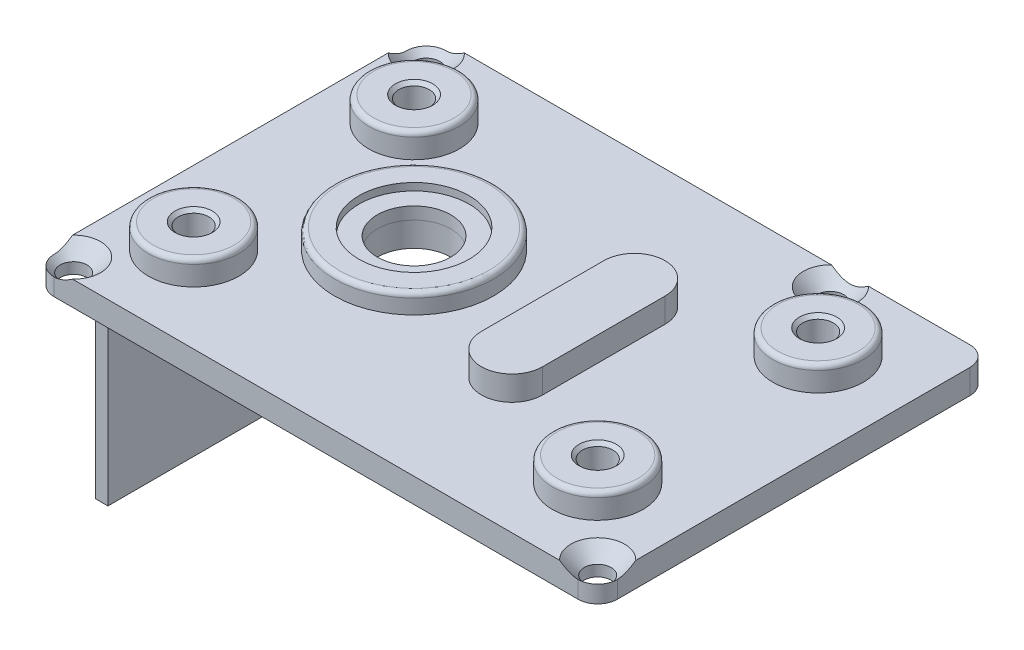
SolidWorks part; units mm, degrees
material "201.0-T7 Insulated Mold Casting (SS)"
ref_plane "Front Plane" through (0, 0, 0) normal (0, 0, 1) x (1, 0, 0)
ref_plane "Top Plane" through (0, 0, 0) normal (0, 1, 0) x (1, 0, 0)
ref_plane "Right Plane" through (0, 0, 0) normal (1, 0, 0) x (0, 0, -1)
sketch "Sketch2" plane through (0, 0, 0) normal (0, 1, 0) x (1, 0, 0)
  line L0 (0, 0) -> (-15, 0) construction
  line L1 (-15, 16) -> (31, 16)
  line L2 (-15, 16) -> (-15, -16)
  line L3 (-15, -16) -> (31, -16)
  line L4 (31, 16) -> (31, -16)
  dimension "D1" = 32
  dimension "D2" = 46
  dimension "D3" = 15
extrude "Boss-Extrude2" add sketch "Sketch2" along normal blind 2
sketch "Sketch6" plane through (0, 2, 0) normal (0, 1, 0) x (1, 0, 0)
  circle A0 centre (0, 0) radius 3
  dimension "D1" = 6
extrude "Cut-Extrude1" cut sketch "Sketch6" against normal through all
sketch "Sketch7" plane through (0, 2, 0) normal (0, 1, 0) x (1, 0, 0)
  circle A0 centre (0, 0) radius 4.5
  circle A1 centre (0, 0) radius 3
  circle A2 centre (0, 0) radius 3 construction
  dimension "D1" = 9
extrude "Boss-Extrude4" add sketch "Sketch7" along normal blind 1 separate body
sketch "Sketch8" plane through (0, 2, 0) normal (0, 1, 0) x (1, 0, 0)
  circle A0 centre (0, 0) radius 4.5
  circle A1 centre (0, 0) radius 4.5 construction
  circle A2 centre (0, 0) radius 6.5
  dimension "D1" = 13
extrude "Boss-Extrude5" add sketch "Sketch8" along normal blind 1.6 separate body
sketch "Sketch3" plane through (0, 2, 0) normal (0, 1, 0) x (1, 0, 0)
  line L0 (-15, 0) -> (31, 0) construction
  line L1 (-15, 16) -> (-15, -16) construction
  line L2 (31, -16) -> (31, 16) construction
  line L3 (8, -16) -> (8, 16) construction
  line L4 (-15, -16) -> (31, -16) construction
  line L5 (31, 16) -> (-15, 16) construction
  circle A0 centre (-9, 9) radius 3.7
  circle A2 centre (0, 0) radius 3 construction
  dimension "D1" = 7.4
  dimension "D2" = 6
  dimension "D4" = 9
  dimension "D3" = 7
  dimension "D5" = 9
extrude "Boss-Extrude3" add sketch "Sketch3" along normal blind 2
fillet "Fillet3" radius 0.4 1 edges at (0, 3.6, 6.5)
ref_plane "MP HORZ HOLES" through (8, 0, 0) normal (-1, 0, 0) x (0, 0, 1)
hole_wizard "M3x0.5 Tapped Hole1" positions "Sketch5" profile "Sketch4" tap size "M3x0.5" standard "ANSI Metric" end condition through all
sketch "Sketch5" plane through (0, 4, 0) normal (0, 1, 0) x (1, 0, 0)
  point P0 (-9, 9)
sketch "Sketch4" plane through (-9, 4, -9) normal (1, 0, 0) x (0, 0, 1)
  line L0 (0, 0) -> (0, 4)
  line L1 (0, 4) -> (1.25, 4)
  line L2 (1.25, 4) -> (1.25, 0.275)
  line L3 (1.25, 0.275) -> (1.525, 0)
  line L5 (1.525, 0) -> (0, 0)
  line L6 (-1.25, 0.275) -> (-1.525, 0) construction
  line L11 (0, -6.35) -> (0, 107.95) construction
  dimension "Thread Major Dia." = 2.5
  dimension "Thru Tap Drill Depth" = 4
  dimension "Near C'Sink Dia." = 3.05
  dimension "Near C'Sink Angle" = 90
pattern_linear "LPattern1" count 2 spacing 33 along (1, 0, 0) of "M3x0.5 Tapped Hole1", "Boss-Extrude3"
sketch "Sketch9" plane through (0, 2, 0) normal (0, 1, 0) x (1, 0, 0)
  line L0 (0, 0) -> (13, 0) construction
  line L1 (13, -5) -> (13, 5) construction
  line L2 (10.5, -5) -> (10.5, 5)
  line L3 (15.5, -5) -> (15.5, 5)
  arc A0 (10.5, -5) -> (15.5, -5) centre (13, -5) ccw
  arc A1 (15.5, 5) -> (10.5, 5) centre (13, 5) ccw
  point P5 (13, 0)
  dimension "D1" = 10
  dimension "D2" = 13
  dimension "D3" = 5
extrude "Boss-Extrude6" add sketch "Sketch9" along normal blind 2
mirror "Mirror2" about plane through (0, 0, 0) normal (0, 0, 1) of "LPattern1", "Boss-Extrude3"
hole_wizard "CSK for M2 Flat Head Machine Screw1" positions "Sketch11" profile "Sketch10" countersink size "M2" standard "ANSI Metric" end condition through all
sketch "Sketch11" plane through (0, 2, 0) normal (0, 1, 0) x (1, 0, 0)
  line L0 (-13.4, 14.4) -> (19.6, 14.4) construction
  line L2 (31, 16) -> (-15, 16) construction
  line L3 (-15, 16) -> (-15, -16) construction
  line L5 (-15, -16) -> (31, -16) construction
  line L6 (29.4, -14.4) -> (-13.4, -14.4) construction
  line L7 (-13.4, 14.4) -> (-13.4, -14.4) construction
  line L9 (31, -16) -> (31, 16) construction
  point P0 (-13.4, 14.4)
  point P4 (19.6, 14.4)
  point P6 (29.4, -14.4)
  point P23 (-13.4, -14.4)
  dimension "D1" = 1.6
  dimension "D2" = 1.6
  dimension "D3" = 1.6
  dimension "D4" = 1.6
  dimension "D5" = 33
sketch "Sketch10" plane through (-13.4, 2, -14.4) normal (1, 0, 0) x (0, 0, 1)
  line L0 (0, 0) -> (0, 2)
  line L1 (0, 2) -> (1.1, 2)
  line L2 (1.1, 2) -> (1.1, 1.1)
  line L3 (1.1, 1.1) -> (2.2, 0)
  line L5 (2.2, 0) -> (0, 0)
  line L6 (-1.1, 1.1) -> (-2.2, 0) construction
  line L11 (0, -6.35) -> (0, 107.95) construction
  dimension "Thru Hole Dia." = 2.2
  dimension "Thru Hole Depth" = 2
  dimension "Near C'Sink Dia." = 4.4
  dimension "Near C'Sink Angle" = 90
fillet "Fillet1" radius 1.6 4 edges at (31, 1, -16) (31, 1, 16) (-15, 1, -16) (-15, 1, 16)
sketch "Sketch12" plane through (0, 0, 0) normal (0, -1, 0) x (1, 0, 0)
  line L0 (-15, -14.4) -> (-15, 14.4) construction
  line L1 (-14, -11) -> (-15, -11)
  line L2 (-14, -11) -> (-14, 11)
  line L3 (-14, 11) -> (-15, 11)
  line L4 (-15, -11) -> (-15, 11)
  line L5 (-14, -11) -> (-15, 11) construction
  line L6 (-14, 11) -> (-15, -11) construction
  line L7 (0, 0) -> (-14.5, 0) construction
  point P0 (-14.5, 0)
  dimension "D1" = 1
  dimension "D2" = 22
extrude "Boss-Extrude7" add sketch "Sketch12" along normal blind 17.6
fillet "Fillet5" radius 0.4 4 edges at (24, 4, 5.3) (-9, 4, 5.3) (24, 4, -5.3) (-9, 4, -5.3)
